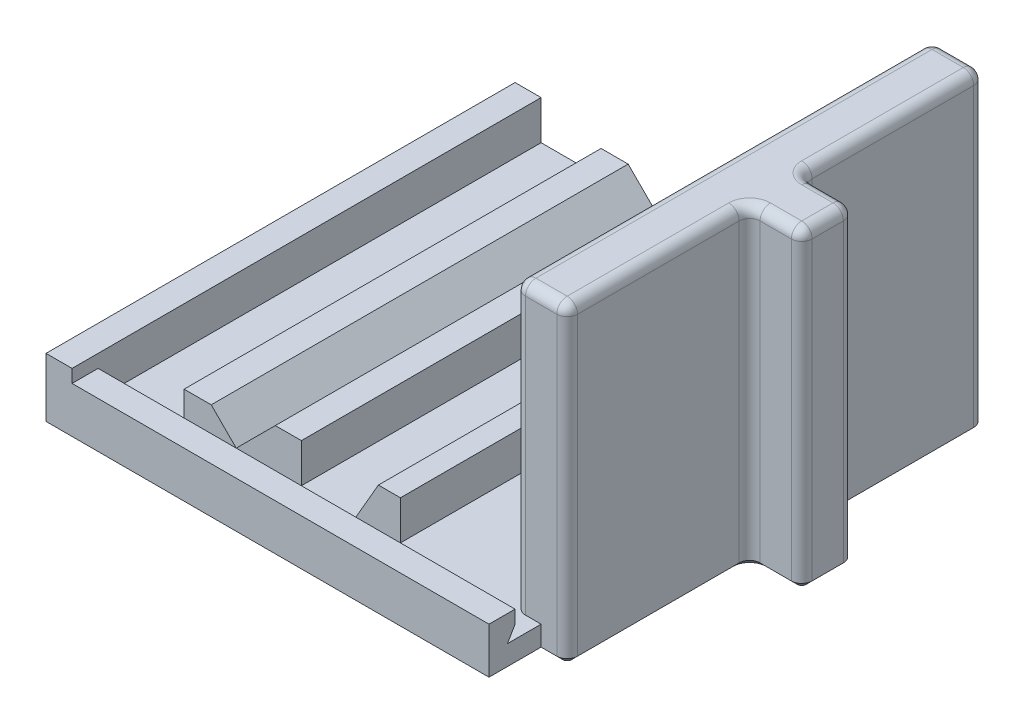
SolidWorks part; units mm, degrees
ref_plane "Front Plane" through (0, 0, 0) normal (0, 0, 1) x (1, 0, 0)
ref_plane "Top Plane" through (0, 0, 0) normal (0, 1, 0) x (1, 0, 0)
ref_plane "Right Plane" through (0, 0, 0) normal (1, 0, 0) x (0, 0, -1)
sketch "Sketch1" plane through (0, 0, 0) normal (0, 1, 0) x (1, 0, 0)
  line L0 (-25.4, 203.2) -> (-25.4, 0)
  line L1 (0, 0) -> (-25.4, 0)
  line L2 (0, 0) -> (0, 203.2)
  line L3 (0, 203.2) -> (-25.4, 203.2)
  line L4 (-25.4, 0) -> (-25.4, 203.2)
  line L5 (-25.4, 203.2) -> (-228.6, 203.2)
  line L6 (-25.4, 0) -> (-228.6, 0)
  line L7 (-228.6, 203.2) -> (-228.6, 0)
  line L8 (0, 101.6) -> (-228.6, 101.6) construction
  line L9 (0, 101.6) -> (104.3179, 101.6)
  line L10 (0, 114.3) -> (0, 88.9)
  line L13 (0, 114.3) -> (25.4, 114.3)
  line L14 (0, 88.9) -> (25.4, 88.9)
  line L15 (25.4, 114.3) -> (25.4, 88.9)
  dimension "D1" = 25.4
  dimension "D2" = 203.2
  dimension "D3" = 88.9
  dimension "D4" = 88.9
  dimension "D5" = 203.2
  dimension "D6" = 25.4
  dimension "D7" = 0
extrude "Boss-Extrude1" add sketch "Sketch1" along normal blind 12.7 contours L8 L0 L5 L7 | L4 L8 L7 L6 region at (-127, 0, -152.4) region at (-127, 0, -50.8)
sketch "Sketch2" plane through (0, 0, 0) normal (0, 1, 0) x (1, 0, 0)
  line L0 (-25.4, 0) -> (-25.4, 203.2)
  line L1 (-25.4, 0) -> (0, 0)
  line L2 (-25.4, 203.2) -> (0, 203.2)
  line L3 (0, 0) -> (0, 203.2)
  dimension "D1" = 25.4
sketch "Sketch3" plane through (0, 0, 0) normal (0, 1, 0) x (1, 0, 0)
  line L0 (0, 88.9) -> (0, 114.3)
  line L1 (0, 88.9) -> (25.4, 88.9)
  line L2 (0, 114.3) -> (25.4, 114.3)
  line L3 (25.4, 88.9) -> (25.4, 114.3)
  line L4 (0, 0) -> (0, 203.2) construction
  line L5 (-25.4, 203.2) -> (-228.6, 203.2) construction
  line L6 (-25.4, 0) -> (-228.6, 0) construction
  dimension "D1" = 88.9
  dimension "D2" = 88.9
  dimension "1" = 25.4
extrude "Boss-Extrude2" add sketch "Sketch2" along normal blind 152.4
extrude "Boss-Extrude3" add sketch "Sketch3" along normal blind 152.4
fillet "Fillet1" radius 5.08 16 edges at (-25.4, 152.4, -101.6) (-12.7, 152.4, -203.2) (0, 152.4, -158.75) (12.7, 152.4, -114.3) (25.4, 152.4, -101.6) (12.7, 152.4, -88.9) (0, 152.4, -44.45) (-12.7, 152.4, 0) (-25.4, 82.55, -203.2) (0, 76.2, -203.2) (0, 76.2, -114.3) (25.4, 76.2, -114.3) (25.4, 76.2, -88.9) (-25.4, 82.55, 0) (0, 76.2, 0) (0, 76.2, -88.9)
sketch "Sketch4" plane through (0, 12.7, 0) normal (0, 1, 0) x (1, 0, 0)
  line L4 (-20.32, 203.2) -> (-228.6, 203.2) construction
  line L5 (-20.32, 0) -> (-228.6, 0) construction
  line L7 (-167.64, 203.2) -> (-167.64, 0)
  line L8 (-167.64, 203.2) -> (-129.54, 203.2)
  line L9 (-167.64, 0) -> (-129.54, 0)
  line L10 (-129.54, 203.2) -> (-129.54, 0)
  line L11 (-106.68, 203.2) -> (-106.68, 0)
  line L12 (-106.68, 203.2) -> (-81.28, 203.2)
  line L13 (-106.68, 0) -> (-81.28, 0)
  line L14 (-81.28, 203.2) -> (-81.28, 0)
  line L15 (-228.6, 203.2) -> (-228.6, 0)
  line L16 (-228.6, 203.2) -> (-215.9, 203.2)
  line L17 (-228.6, 0) -> (-215.9, 0)
  line L18 (-215.9, 203.2) -> (-215.9, 0)
  line L19 (-25.4, 198.12) -> (-25.4, 5.08) construction
  dimension "D3" = 55.88
  dimension "D4" = 38.1
  dimension "D5" = 104.14
  dimension "D6" = 25.4
  dimension "D7" = 12.7
extrude "Boss-Extrude4" add sketch "Sketch4" along normal blind 19.05
chamfer "Chamfer1" distance 25.4 angle 45 1 edges at (-167.64, 31.75, -101.6)
chamfer "Chamfer2" distance 25.4 angle 30 1 edges at (-106.68, 31.75, -101.6) first distance on face at (-106.68, 22.225, -101.6)
sketch "Sketch6" plane through (0, 0, 0) normal (0, 1, 0) x (1, 0, 0)
  line L0 (-228.6, 0) -> (-12.7, 0)
  line L1 (-228.6, 0) -> (-228.6, -25.4)
  line L2 (-12.7, 0) -> (-12.7, -25.4)
  line L3 (-228.6, -25.4) -> (-12.7, -25.4)
  line L4 (-20.32, 0) -> (-81.28, 0) construction
  dimension "D1" = 25.4
  dimension "D2" = 215.9
sketch "Sketch7" plane through (0, 0, 0) normal (0, 0, 1) x (1, 0, 0)
  line L0 (-103.0138, 12.7) -> (-92.0153, 31.75)
  line L1 (-92.0153, 31.75) -> (19.7826, 225.3896)
  line L2 (-161.29, 12.7) -> (-142.24, 31.75)
  line L3 (-142.24, 31.75) -> (6.7651, 180.7551)
extrude "Boss-Extrude6" add sketch "Sketch6" along normal blind 12.7
sketch "Sketch8" plane through (0, 12.7, 0) normal (0, 1, 0) x (1, 0, 0)
  line L0 (-228.6, -25.4) -> (-12.7, -25.4)
  line L1 (-228.6, -25.4) -> (-228.6, -12.7)
  line L2 (-12.7, -25.4) -> (-12.7, -12.7)
  line L3 (-228.6, -12.7) -> (-12.7, -12.7)
  dimension "D1" = 12.7
extrude "Boss-Extrude7" add sketch "Sketch8" along normal blind 12.7
sketch "Sketch9" plane through (0, 0, 12.7) normal (0, 0, -1) x (-1, 0, 0)
  line L0 (228.6, 12.7) -> (12.7, 12.7)
  line L1 (228.6, 12.7) -> (228.6, 19.05)
  line L2 (12.7, 12.7) -> (12.7, 19.05)
  line L3 (228.6, 19.05) -> (12.7, 19.05)
  dimension "D1" = 6.35
sketch "Sketch10" plane through (0, 12.7, 0) normal (0, 1, 0) x (1, 0, 0)
  line L0 (-161.29, 203.2) -> (-161.29, 0)
  line L1 (-161.29, 203.2) -> (-186.69, 203.2)
  line L2 (-161.29, 0) -> (-186.69, 0)
  line L3 (-186.69, 203.2) -> (-186.69, 0)
  dimension "D1" = 25.4
extrude "Boss-Extrude8" add sketch "Sketch10" along normal blind 12.192
chamfer "Chamfer3" distance 12.192 angle 45 1 edges at (-161.29, 24.892, -101.6)
chamfer "Chamfer4" distance 3 angle 45 16 edges at (-228.6, 0, -88.9) (-120.65, 0, 25.4) (-12.7, 0, 12.7) (-8.89, 0, 0) (-1.4879, 0, -1.4879) (0, 0, -44.45) (1.4879, 0, -87.4121) (12.7, 0, -88.9) (23.9121, 0, -90.3879) (25.4, 0, -101.6) (23.9121, 0, -112.8121) (12.7, 0, -114.3) (1.4879, 0, -115.7879) (0, 0, -158.75) (-1.4879, 0, -201.7121) (-116.84, 0, -203.2)
extrude "Cut-Extrude2" cut sketch "Sketch9" against normal blind 6.35
chamfer "Chamfer5" distance 6.35 angle 60 1 edges at (-120.65, 19.05, 19.05) first distance on face at (-120.65, 19.05, 15.875)
sketch "Sketch11" plane through (0, 0, 0) normal (0, 0, 1) x (1, 0, 0)
  line L1 (-228.6, 31.75) -> (-215.9, 31.75)
  line L2 (-228.6, 31.75) -> (-228.6, 12.7)
  line L3 (-228.6, 12.7) -> (-215.9, 12.7)
  line L4 (-215.9, 31.75) -> (-215.9, 12.7)
extrude "Boss-Extrude9" add sketch "Sketch11" along normal blind 25.4
